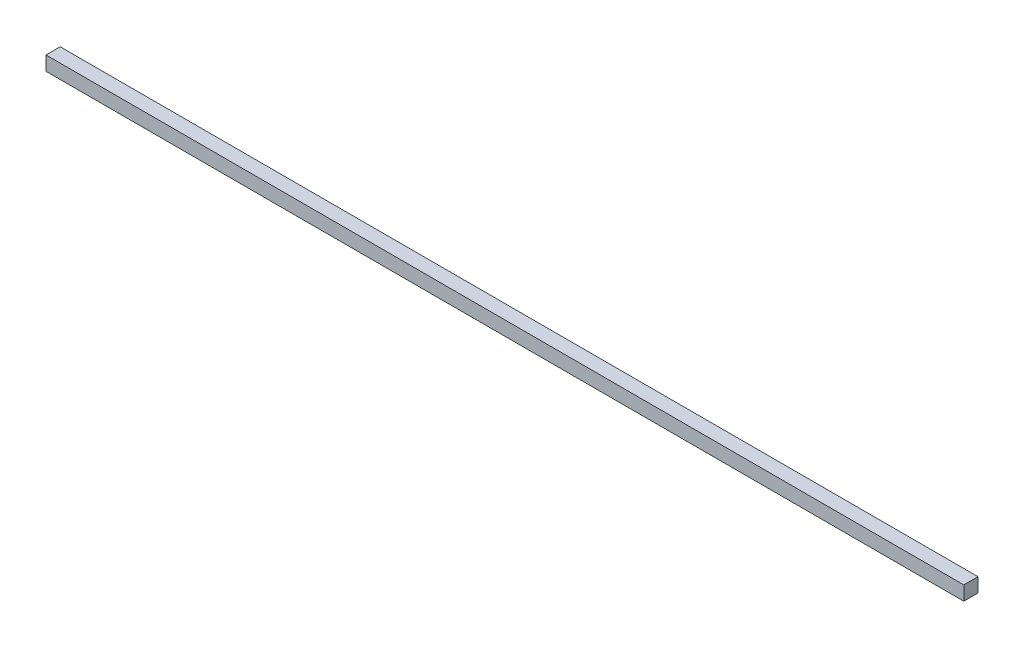
SolidWorks part; units mm, degrees
ref_plane "Front Plane" through (0, 0, 0) normal (0, 0, 1) x (1, 0, 0)
ref_plane "Top Plane" through (0, 0, 0) normal (0, 1, 0) x (1, 0, 0)
ref_plane "Right Plane" through (0, 0, 0) normal (1, 0, 0) x (0, 0, -1)
sketch "Sketch1" plane through (0, 0, 0) normal (1, 0, 0) x (0, 0, -1)
  line L1 (0, 0) -> (4.7625, 0)
  line L2 (0, 0) -> (0, 4.7625)
  line L3 (0, 4.7625) -> (4.7625, 4.7625)
  line L4 (4.7625, 0) -> (4.7625, 4.7625)
  dimension "D1" = 4.7625
extrude "Boss-Extrude1" add sketch "Sketch1" against normal blind 307.975 contours L1 L4 L3 L2 region at (0, 2.3813, -2.3813)
move or copy body "Body-Move/Copy1" [suppressed] bodies to move or copy 101 parameters "D1"=0, "D2"=0, "D3"=0
move or copy body "Body-Move/Copy2" [suppressed] bodies to move or copy 102 parameters "D1"=0, "D2"=0, "D3"=0
move or copy body "Body-Move/Copy3" [suppressed] bodies to move or copy 103 parameters "D1"=0, "D2"=0, "D3"=0
move or copy body "Body-Move/Copy4" [suppressed] bodies to move or copy 104 parameters "D1"=0, "D2"=0, "D3"=0
move or copy body "Body-Move/Copy5" [suppressed] bodies to move or copy 105 parameters "D1"=0, "D2"=0, "D3"=0
move or copy body "Body-Move/Copy6" [suppressed] bodies to move or copy 106 parameters "D1"=0, "D2"=0, "D3"=0
move or copy body "Body-Move/Copy7" [suppressed] bodies to move or copy 107 parameters "D1"=0, "D2"=0, "D3"=0
move or copy body "Body-Move/Copy8" [suppressed] bodies to move or copy 108 parameters "D1"=0, "D2"=0, "D3"=0
move or copy body "Body-Move/Copy9" [suppressed] bodies to move or copy 109 parameters "D1"=0, "D2"=0, "D3"=0
move or copy body "Body-Move/Copy10" [suppressed] bodies to move or copy 110 parameters "D1"=0, "D2"=0, "D3"=0
